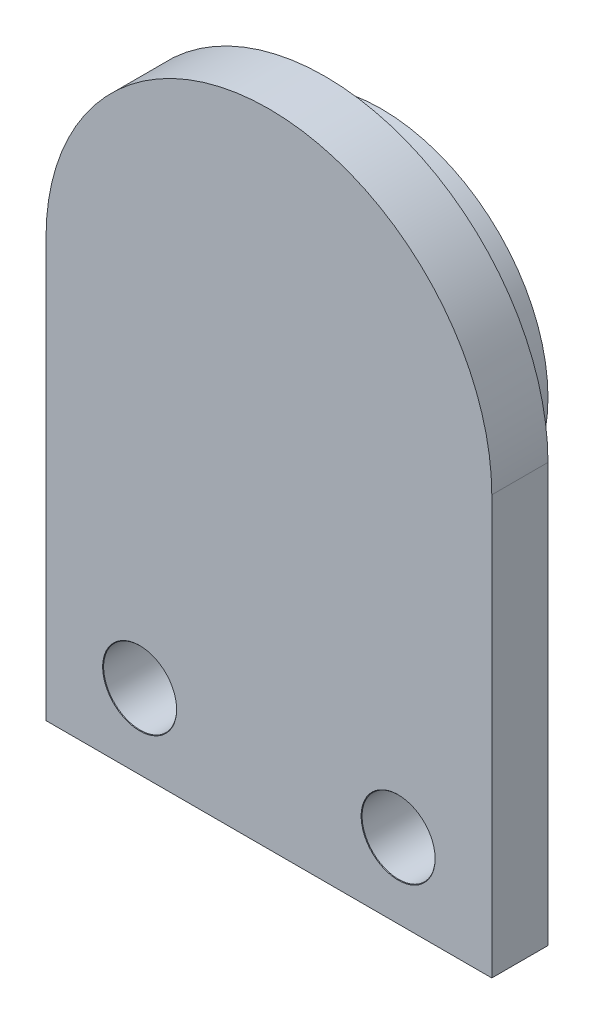
SolidWorks part; units mm, degrees
ref_plane "Front Plane" through (0, 0, 0) normal (0, 0, 1) x (1, 0, 0)
ref_plane "Top Plane" through (0, 0, 0) normal (0, 1, 0) x (1, 0, 0)
ref_plane "Right Plane" through (0, 0, 0) normal (1, 0, 0) x (0, 0, -1)
sketch "Sketch1" plane through (0, 0, 0) normal (0, 0, 1) x (1, 0, 0)
  line L0 (-11.9, 0) -> (-11.9, -22.34)
  line L1 (-11.9, -22.34) -> (11.9, -22.34)
  line L2 (11.9, -22.34) -> (11.9, 0)
  arc A0 (11.9, 0) -> (-11.9, 0) centre (0, 0) ccw
  dimension "D1" = 22.34
  dimension "D2" = 23.8
extrude "Boss-Extrude1" add sketch "Sketch1" along normal blind 3
sketch "Sketch2" plane through (0, 0, 0) normal (0, 0, -1) x (-1, 0, 0)
  circle A0 centre (0, 0) radius 8.9
  dimension "D1" = 17.8
extrude "Boss-Extrude2" add sketch "Sketch2" along normal blind 3
sketch "Sketch3" plane through (0, 0, -3) normal (0, 0, -1) x (-1, 0, 0)
  circle A0 centre (0, 0) radius 2
  point P3 (0, 0)
  dimension "D1" = 4
extrude "Boss-Extrude3" add sketch "Sketch3" along normal blind 3
hole_wizard "M3.5 Clearance Hole1" positions "3DSketch1" profile "Sketch5" hole size "M3.5" standard "ANSI Metric" end condition through all
sketch3d "3DSketch1"
  line L0 (-11.9, -22.34, 3) -> (11.9, -22.34, 3) construction
  line L1 (-11.9, 0, 3) -> (-11.9, -22.34, 3) construction
  line L2 (11.9, -22.34, 3) -> (11.9, 0, 3) construction
  point P0 (-6.9, -18.34, 3)
  point P2 (6.9, -18.34, 3)
  dimension "D1" = 4
  dimension "D2" = 5
  dimension "D3" = 5
sketch "Sketch5" plane through (-6.9, -18.34, 3) normal (1, 0, 0) x (0, -1, 0)
  line L0 (0, 0) -> (0, 9)
  line L1 (0, 9) -> (1.95, 9)
  line L2 (1.95, 9) -> (1.95, 0.025)
  line L3 (1.95, 0.025) -> (1.975, 0)
  line L5 (1.975, 0) -> (0, 0)
  line L6 (-1.95, 0.025) -> (-1.975, 0) construction
  line L11 (0, -6.35) -> (0, 107.95) construction
  dimension "Thru Hole Dia." = 3.9
  dimension "Thru Hole Depth" = 9
  dimension "Near C'Sink Dia." = 3.95
  dimension "Near C'Sink Angle" = 90
